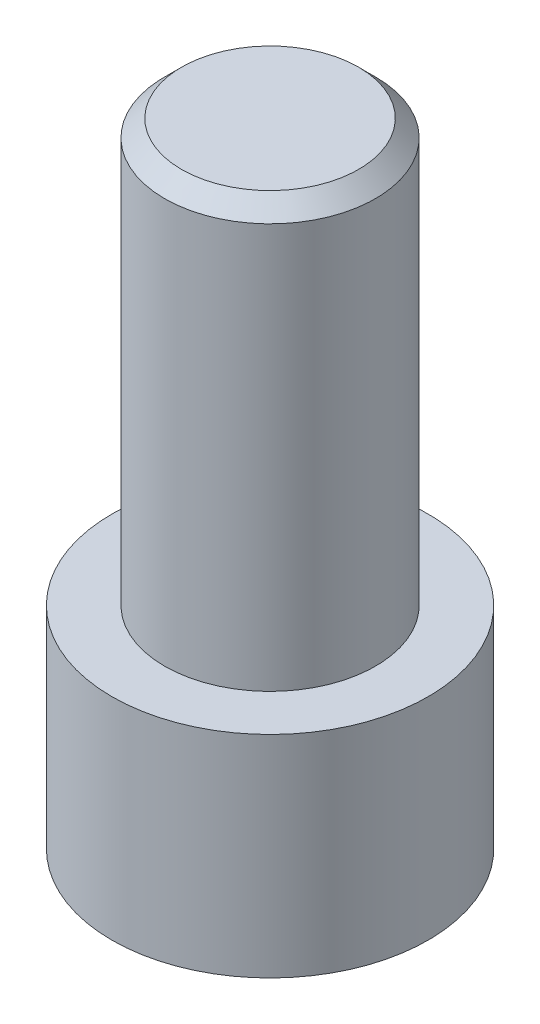
SolidWorks part; units mm, degrees
material "Plain Carbon Steel"
ref_plane "Front Plane" through (0, 0, 0) normal (0, 0, 1) x (1, 0, 0)
ref_plane "Top Plane" through (0, 0, 0) normal (0, 1, 0) x (1, 0, 0)
ref_plane "Right Plane" through (0, 0, 0) normal (1, 0, 0) x (0, 0, -1)
sketch "Sketch1" plane through (0, 0, 0) normal (0, 1, 0) x (1, 0, 0)
  circle A0 centre (0, 0) radius 3.175
  circle A1 centre (0, 0) radius 4.7625
  dimension "D1" = 9.525
  dimension "D2" = 6.35
extrude "Boss-Extrude1" add sketch "Sketch1" against normal blind 6.35 contours A0 | A1 A0 region at (0, 0, 0) region at (-4.6278, 0, 0)
extrude "Boss-Extrude2" add sketch "Sketch1<3>" along normal blind 12.7 contours A0 region at (0, 0, 0)
sketch "Sketch1<3>" plane through (0, 0, 0) normal (0, 1, 0) x (1, 0, 0) same geometry as "Sketch1"
chamfer "Chamfer1" distance 0.508 angle 45 1 edges at (0, 12.7, 3.175)
sketch "Sketch2" plane through (0, -6.35, 0) normal (0, -1, 0) x (1, 0, 0)
  line L1 (1.27, -2.1997) -> (2.54, 0)
  line L2 (2.54, 0) -> (1.27, 2.1997)
  line L3 (1.27, 2.1997) -> (-1.27, 2.1997)
  line L4 (-1.27, 2.1997) -> (-2.54, 0)
  line L5 (-2.54, 0) -> (-1.27, -2.1997)
  line L6 (-1.27, -2.1997) -> (1.27, -2.1997)
  circle A0 centre (0, 0) radius 2.1997 construction
  point P1 (2.5334, 0.1834)
  point P10 (0, 0)
  dimension "D1" = 5.08
extrude "Cut-Extrude1" cut sketch "Sketch2" against normal blind 3.81
